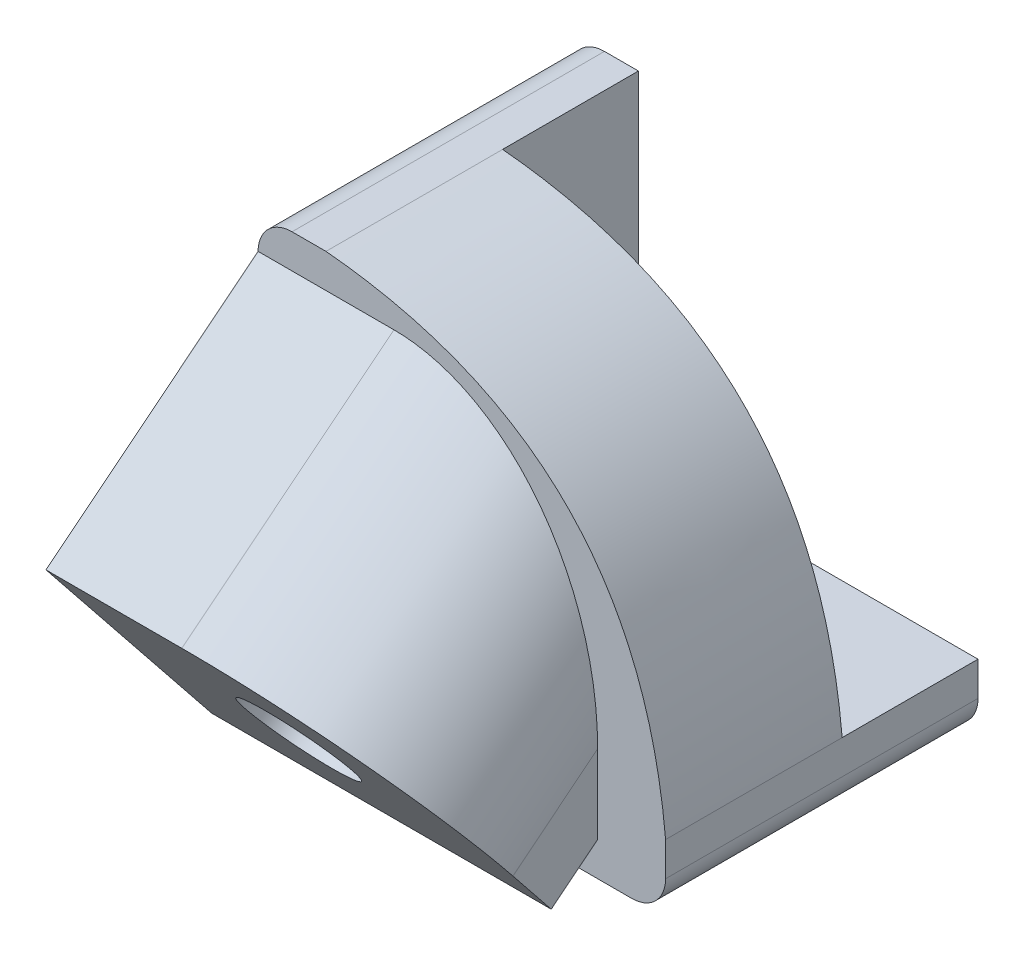
SolidWorks part; units mm, degrees
ref_plane "Front Plane" through (0, 0, 0) normal (0, 0, 1) x (1, 0, 0)
ref_plane "Top Plane" through (0, 0, 0) normal (0, 1, 0) x (1, 0, 0)
ref_plane "Right Plane" through (0, 0, 0) normal (1, 0, 0) x (0, 0, -1)
sketch "Sketch1" plane through (0, 0, 0) normal (0, 0, 1) x (1, 0, 0)
  line L0 (0, 0) -> (12.7, 0)
  line L1 (0, 0) -> (0, 12.7)
  circle A0 centre (5.08, 5.08) radius 3.1115
  spline S0 degree 2 poles (0, 12.7) (11.6203, 11.6203) (12.7, 0) knots 0 0 0 1 1 1
  dimension "D5" = 6.223
  dimension "D1" = 12.7
  dimension "D2" = 12.7
  dimension "D3" = 5.08
  dimension "D4" = 5.08
extrude "Boss-Extrude1" add sketch "Sketch1" along normal blind 3.81
sketch "Sketch2" plane through (0, 0, 0) normal (0, 0, -1) x (-1, 0, 0)
  line L0 (0, 12.7) -> (1.27, 12.7)
  line L1 (2.54, 11.43) -> (2.54, -1.27)
  line L2 (0, 12.7) -> (0, 0) construction
  line L3 (-12.7, 0) -> (-12.7, -1.27)
  line L4 (-11.43, -2.54) -> (1.27, -2.54)
  line L5 (0, 12.7) -> (0, 0)
  line L6 (0, 0) -> (-12.7, 0)
  arc A0 (1.27, 12.7) -> (2.54, 11.43) centre (1.27, 11.43) cw
  arc A1 (-12.7, -1.27) -> (-11.43, -2.54) centre (-11.43, -1.27) ccw
  arc A2 (1.27, -2.54) -> (2.54, -1.27) centre (1.27, -1.27) ccw
  point P14 (-12.7, -2.54)
  dimension "D3" = 1.27
  dimension "D1" = 2.54
  dimension "D2" = 2.54
extrude "Boss-Extrude2" add sketch "Sketch2" along normal blind 5.08 and the other way blind 3.81 contours L1 A2 L4 A1 L3 L6 L5 L0 A0
sketch "Sketch3" plane through (0, 0, 3.81) normal (0, 0, 1) x (1, 0, 0)
  line L0 (-2.54, 11.43) -> (-2.54, -1.27)
  line L1 (-1.27, -2.54) -> (11.43, -2.54)
  line L2 (12.7, -1.27) -> (12.7, 0)
  line L3 (-1.27, 12.7) -> (0, 12.7)
  arc A0 (11.43, -2.54) -> (12.7, -1.27) centre (11.43, -1.27) ccw
  arc A1 (-2.54, 11.43) -> (-1.27, 12.7) centre (-1.27, 11.43) cw
  arc A3 (-2.54, -1.27) -> (-1.27, -2.54) centre (-1.27, -1.27) ccw
  spline S0 degree 2 poles (0, 12.7) (11.6203, 11.6203) (12.7, 0) knots 0 0 0 1 1 1
  dimension "D1" = 1.27
  dimension "D3" = 1.27
extrude "Boss-Extrude3" add sketch "Sketch3" along normal blind 0.254
sketch "Sketch4" plane through (0, 0, 4.064) normal (0, 0, 1) x (1, 0, 0)
  line L0 (-2.54, 11.43) -> (-2.54, -1.27)
  line L1 (-1.27, -2.54) -> (11.43, -2.54)
  line L2 (12.7, -1.27) -> (12.7, 0)
  line L3 (-1.27, 12.7) -> (0, 12.7)
  arc A0 (11.43, -2.54) -> (12.7, -1.27) centre (11.43, -1.27) ccw
  arc A1 (-2.54, 11.43) -> (-1.27, 12.7) centre (-1.27, 11.43) cw
  arc A3 (-2.54, -1.27) -> (-1.27, -2.54) centre (-1.27, -1.27) ccw
  spline S0 degree 2 poles (0, 12.7) (11.6203, 11.6203) (12.7, 0) knots 0 0 0 1 1 1
  dimension "D1" = 1.27
  dimension "D3" = 1.27
extrude "Boss-Extrude4" add sketch "Sketch4" along normal blind 2.54
sketch "Sketch10" plane through (-2.54, 0, 0) normal (-1, 0, 0) x (0, 0, 1)
  line L0 (6.604, 11.43) -> (14.5354, 5.0803)
  line L1 (14.5354, 5.0803) -> (8.3393, -2.6592)
  line L2 (8.3393, -2.6592) -> (6.604, -1.27)
  line L3 (6.604, -1.27) -> (6.604, 11.43)
  line L4 (6.604, 11.43) -> (-5.08, 11.43) construction
  line L5 (6.604, -1.27) -> (-5.08, -1.27) construction
  dimension "D1" = 141.32
  dimension "D2" = 141.32
  dimension "D3" = 10.16
extrude "Boss-Extrude5" add sketch "Sketch10" against normal blind 12.7
fillet "Fillet1" radius 7.62 1 edges at (10.16, 8.2552, 10.5697)
sketch "Sketch11" plane through (0, -5.1073, 6.3795) normal (0, -0.625, 0.7806) x (1, 0, 0)
  circle A0 centre (3.81, 8.093) radius 2
  dimension "D1" = 4
extrude "Cut-Extrude1" cut sketch "Sketch11" against normal blind 7 contours A0
